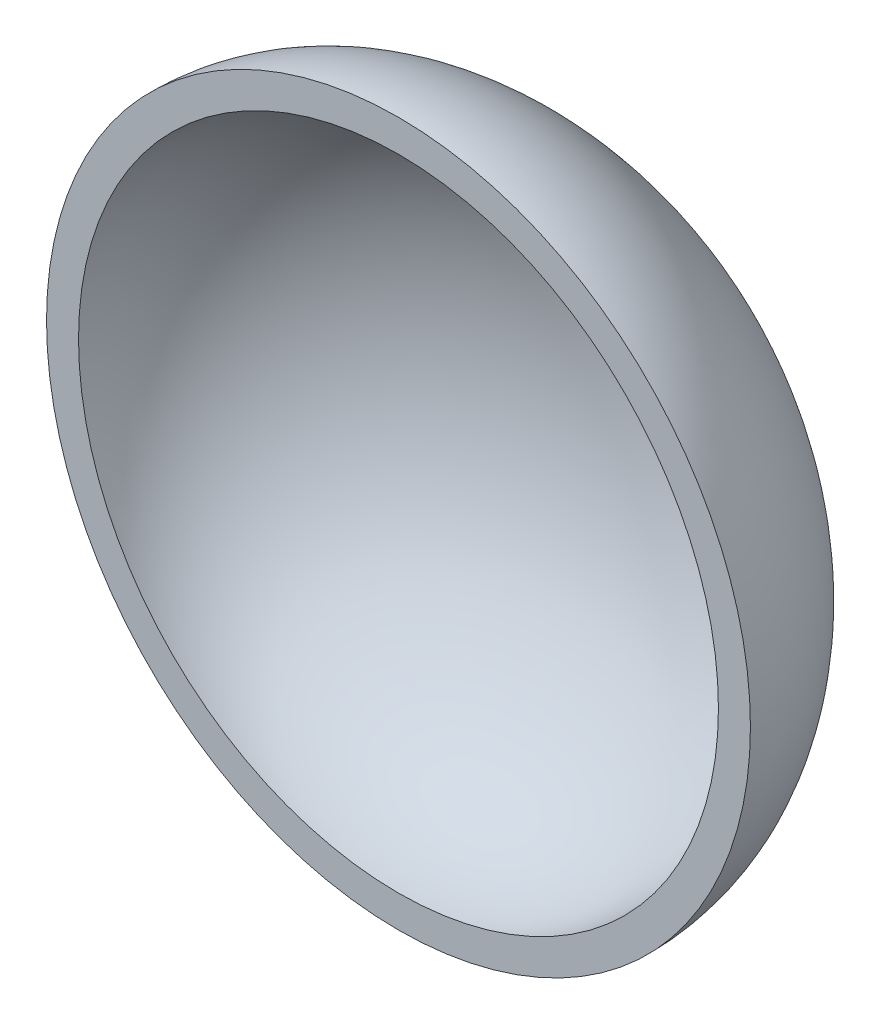
SolidWorks part; units mm, degrees
ref_plane "前视基准面" through (0, 0, 0) normal (0, 0, 1) x (1, 0, 0)
ref_plane "上视基准面" through (0, 0, 0) normal (0, 1, 0) x (1, 0, 0)
ref_plane "右视基准面" through (0, 0, 0) normal (1, 0, 0) x (0, 0, -1)
sketch "草图1" plane through (0, 0, 0) normal (0, 1, 0) x (1, 0, 0)
  line L0 (-22, 0) -> (-20, 0)
  line L1 (0, 16) -> (0, 14)
  ellipse E0 centre (0, 0) end of major axis (22, 0) minor radius 16 (0, 16) -> (-22, 0) ccw
  ellipse E1 centre (0, 0) end of major axis (20, 0) minor radius 14 (0, 14) -> (-20, 0) ccw
revolve "旋转1" add sketch "草图1" angle 360 about L1
sketch "草图2" plane through (0, 0, 0) normal (0, 0, 1) x (1, 0, 0)
  circle A1 centre (0, 0) radius 2.75
sketch "草图4" plane through (0, 0, 0) normal (0, 1, 0) x (1, 0, 0)
  line L0 (-22, 0) -> (-22, -15)
  ellipse E0 centre (0, 0) end of major axis (-22, 0) minor radius 16 (0, 16) -> (-22, 0) ccw
  ellipse E1 centre (0, 0) end of major axis (22, 0) minor radius 16 (0, 16) -> (-22, 0) ccw construction
sketch "草图14" plane through (0, 0, 0) normal (0, 0, 1) x (1, 0, 0)
  circle A0 centre (0, 0) radius 28
  circle A1 centre (0, 0) radius 30
extrude "凸台-拉伸1" [suppressed] add sketch "草图14" along normal blind 15
sketch "草图6" plane through (0, 0, 0) normal (0, 1, 0) x (1, 0, 0)
  line L0 (0, 12.5921) -> (0, -12.3115) construction
extrude "切除-拉伸2" [suppressed] cut sketch "草图2" against normal through all contours A1
pattern_circular "阵列(圆周)2" [suppressed] count 9 over 360 about axis through (0, 0, -12.5921) along (0, 0, 1) of bodies 118
sketch "草图11" plane through (0, 0, 0) normal (0, 0, 1) x (1, 0, 0)
  line L0 (4.9497, 6.364) -> (6.364, 4.9497)
  line L1 (-4.9497, -6.364) -> (-6.364, -4.9497)
  line L2 (6.364, 4.9497) -> (-4.9497, -6.364)
  line L3 (4.9497, 6.364) -> (-6.364, -4.9497)
pattern_circular "阵列(圆周)5" [suppressed] count 7 over 360 about axis through (0, 0, -12.5921) along (0, 0, 1) of bodies 119
pattern_circular "阵列(圆周)8" [suppressed] count 8 over 360 about axis through (0, 0, -12.5921) along (0, 0, 1) of bodies 119
ref_plane "基准面1" [suppressed] through (0, 0, -13.867) normal (0, 0, 1) x (1, 0, 0)
sketch "草图15" [suppressed] plane through (0, 0, -13.867) normal (0, 0, 1) x (1, 0, 0)
  circle A0 centre (0, 0) radius 2.5
  circle A1 centre (0, 0) radius 2.45
ref_plane "基准面2" [suppressed] through (0, 0, -15.8745) normal (0, 0, 1) x (1, 0, 0)
extrude "凸台-拉伸2" [suppressed] add sketch "草图15" against normal blind 2
pattern_curve "曲线阵列1" [suppressed] of bodies 113 driven by "草图4" parameters "D1"=2, "D3"=20, "D2"=1, "D4"=10
sketch "草图17" plane through (0, 0, 0) normal (0, 1, 0) x (1, 0, 0)
  line L0 (0, 21.5636) -> (0, -17.5498) construction
ref_plane "基准面5" [suppressed] through (-12.6303, 0, -11.844) normal (0.7294, 0, 0.684) x (0.684, 0, -0.7294)
sketch "草图21" [suppressed] plane through (-12.6303, 0, -11.844) normal (0.7294, 0, 0.684) x (0.684, 0, -0.7294)
  circle A0 centre (-5.8567, 0) radius 2.5
  circle A1 centre (-5.8567, 0) radius 2.5
extrude "切除-拉伸4" [suppressed] cut sketch "草图21" against normal through all both and the other way through all contours A0
sketch "草图22" [suppressed] plane through (-12.6303, 0, -11.844) normal (0.7294, 0, 0.684) x (0.684, 0, -0.7294)
  circle A0 centre (-5.8567, 0) radius 2.5
  circle A1 centre (-5.8567, 0) radius 2.2
extrude "凸台-拉伸5" [suppressed] add sketch "草图22" against normal blind 0.8
pattern_circular "阵列(圆周)28" [suppressed] count 7 over 360 about axis through (0, 0, -21.5636) along (0, 0, 1) of bodies 129
pattern_circular "阵列(圆周)29" [suppressed] count 7 over 360 about axis through (0, 0, -21.5636) along (0, 0, 1) of bodies 142
sketch "草图23" [suppressed] plane through (0, 0, 15) normal (0, 0, 1) x (1, 0, 0)
  circle A0 centre (0, 0) radius 28
  circle A1 centre (0, 0) radius 29
extrude "凸台-拉伸6" [suppressed] add sketch "草图23" along normal blind 2
sketch "草图24" plane through (0, 0, 0) normal (0, 0, 1) x (1, 0, 0)
  line L2 (-21.9773, 1) -> (-21.1764, 1)
  line L4 (-21.9773, -1) -> (-21.1764, -1)
  circle A0 centre (0, 0) radius 20
  arc A2 (-21.1764, -1) -> (-21.1764, 1) centre (0, 0) ccw
  arc A3 (-21.9773, 1) -> (-21.9773, -1) centre (0, 0) ccw
extrude "凸台-拉伸7" [suppressed] add sketch "草图24" along normal blind 2
chamfer "倒角1" [suppressed] distance 0.3 angle 45
